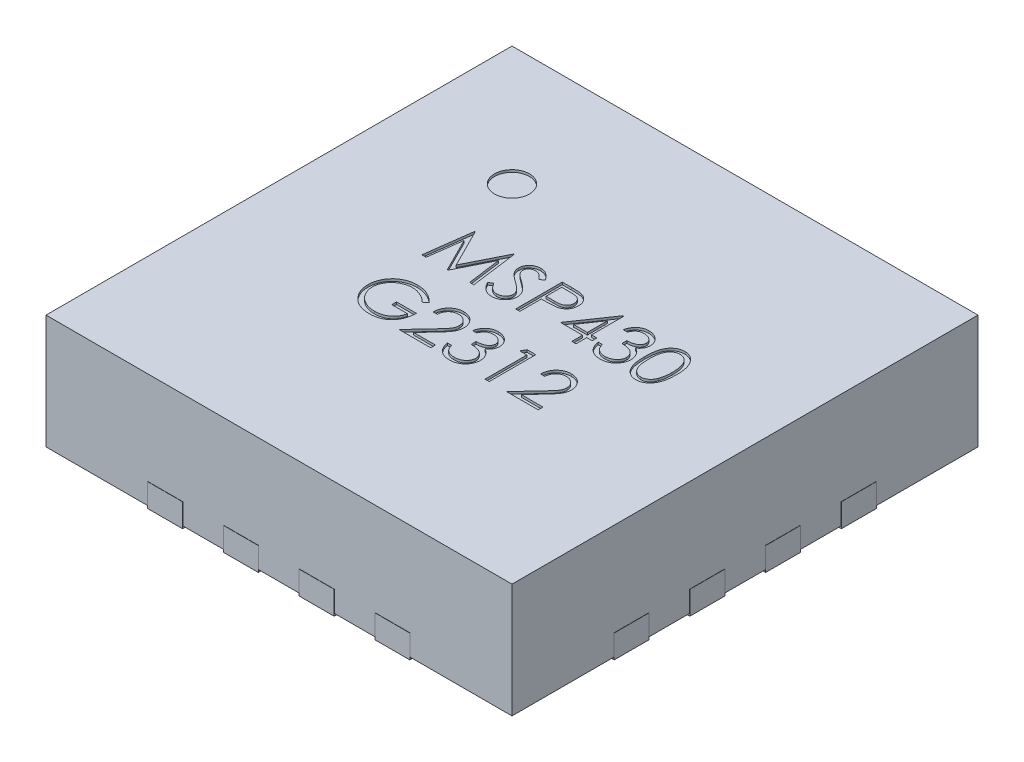
SolidWorks part; units mm, degrees
ref_plane "Front Plane" through (0, 0, 0) normal (0, 0, 1) x (1, 0, 0)
ref_plane "Top Plane" through (0, 0, 0) normal (0, 1, 0) x (1, 0, 0)
ref_plane "Right Plane" through (0, 0, 0) normal (1, 0, 0) x (0, 0, -1)
ref_plane "Plane1" through (0, 0.02, 0) normal (0, 1, 0) x (1, 0, 0)
sketch "Sketch1" plane through (0, 0.02, 0) normal (0, 1, 0) x (1, 0, 0)
  line L1 (-2, 2) -> (2, 2)
  line L2 (-2, 2) -> (-2, -2)
  line L3 (-2, -2) -> (2, -2)
  line L4 (2, 2) -> (2, -2)
  line L5 (-2, 2) -> (2, -2) construction
  line L6 (-2, -2) -> (2, 2) construction
  point P0 (0, 0)
  dimension "D1" = 4
  dimension "D2" = 4
extrude "Boss-Extrude1" add sketch "Sketch1" along normal blind 0.98
sketch "Sketch2" plane through (0, 0.02, 0) normal (0, -1, 0) x (1, 0, 0)
  line L0 (1.75, -0.825) -> (2, -0.825)
  line L1 (2, 2) -> (2, -2) construction
  line L2 (2, -0.825) -> (2, -1.125)
  line L3 (2, -1.125) -> (1.75, -1.125)
  arc A0 (1.75, -0.825) -> (1.75, -1.125) centre (1.75, -0.975) ccw
  dimension "D1" = 0.3
  dimension "D2" = 0.25
  dimension "D3" = 0.825
extrude "Boss-Extrude2" add sketch "Sketch2" along normal blind 0.02
pattern_linear "LPattern2" count 4 spacing 0.65 along (0, 0, 1) of "Boss-Extrude2"
sketch "Sketch3" plane through (0, 0, 0) normal (0, 0, 1) x (1, 0, 0)
  line L0 (0, 0) -> (0, 1.048) construction
ref_axis "Axis1" through (0, 0, 0) along (0, 1, 0)
pattern_circular "CirPattern1" count 4 over 360 about axis through (0, 0, 0) along (0, 1, 0) of "Boss-Extrude2", "LPattern2"
sketch "Sketch4" plane through (0, 0.02, 0) normal (0, -1, 0) x (1, 0, 0)
  line L0 (-1.35, -1.05) -> (-1.05, -1.35)
  line L1 (-1.35, 1.35) -> (1.35, 1.35)
  line L2 (-1.35, 1.35) -> (-1.35, -1.05)
  line L3 (-1.05, -1.35) -> (1.35, -1.35)
  line L4 (1.35, 1.35) -> (1.35, -1.35)
  line L5 (-1.35, 1.35) -> (1.35, -1.35) construction
  line L6 (-1.35, -1.35) -> (1.35, 1.35) construction
  point P0 (0, 0)
  dimension "D1" = 2.7
  dimension "D2" = 2.7
extrude "Boss-Extrude3" add sketch "Sketch4" along normal blind 0.02
sketch "Sketch5" plane through (0, 1, 0) normal (0, 1, 0) x (1, 0, 0)
  circle A0 centre (-0.975, 0.975) radius 0.15
  dimension "D1" = 0.3
  dimension "D2" = 0.975
  dimension "D3" = 0.975
extrude "Cut-Extrude1" cut sketch "Sketch5" against normal blind 0.02
sketch "Sketch6" plane through (0, 1, 0) normal (0, 1, 0) x (1, 0, 0)
  text T0 "MSP430" font "Century Gothic" height 0.4
sketch "Sketch7" plane through (0, 1, 0) normal (0, 1, 0) x (1, 0, 0)
  text T0 "G2312" font "Century Gothic" height 0.4
extrude "Cut-Extrude2" cut sketch "Sketch7" against normal blind 0.02
extrude "Cut-Extrude3" cut sketch "Sketch6" against normal blind 0.02
sketch "Sketch8" plane through (-2, 0, 0) normal (-1, 0, 0) x (0, 0, 1)
  line L0 (-0.825, 0) -> (-0.825, 0.02) construction
  line L1 (-1.125, 0) -> (-0.825, 0)
  line L2 (-1.125, 0) -> (-1.125, 0.2)
  line L3 (-1.125, 0.2) -> (-0.825, 0.2)
  line L4 (-0.825, 0) -> (-0.825, 0.2)
  dimension "D1" = 0.2
extrude "Boss-Extrude4" add sketch "Sketch8" along normal blind 0.002
pattern_linear "LPattern3" count 4 spacing 0.65 along (0, 0, 1) of "Boss-Extrude4"
pattern_circular "CirPattern2" count 4 over 360 about axis through (0, 0, 0) along (0, 1, 0) of "LPattern3"
